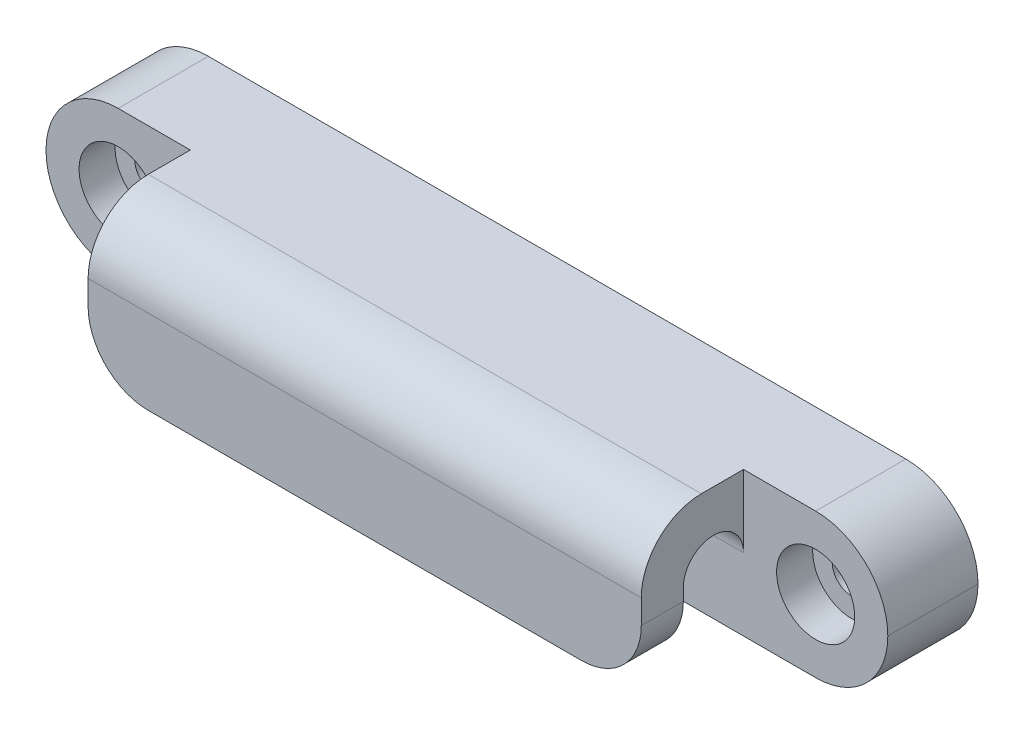
SolidWorks part; units mm, degrees
ref_plane "Front Plane" through (0, 0, 0) normal (0, 0, 1) x (1, 0, 0)
ref_plane "Top Plane" through (0, 0, 0) normal (0, 1, 0) x (1, 0, 0)
ref_plane "Right Plane" through (0, 0, 0) normal (1, 0, 0) x (0, 0, -1)
sketch "Sketch1" plane through (0, 0, 0) normal (0, 0, 1) x (1, 0, 0)
  line L1 (-35, 6) -> (35, 6)
  line L2 (-35, 6) -> (-35, -6)
  line L3 (-35, -6) -> (35, -6)
  line L4 (35, 6) -> (35, -6)
  line L5 (-35, 6) -> (35, -6) construction
  line L6 (-35, -6) -> (35, 6) construction
  point P0 (0, 0)
  dimension "D1" = 12
  dimension "D2" = 70
extrude "Boss-Extrude1" add sketch "Sketch1" along normal blind 16
sketch "Sketch2" plane through (-35, 0, 0) normal (-1, 0, 0) x (0, 0, 1)
  line L0 (0, 6) -> (16, -6) construction
  line L1 (0, 0) -> (16, 0) construction
  line L2 (16, 6) -> (16, -6) construction
  circle A0 centre (10, 0) radius 2.5
  dimension "D1" = 5
  dimension "D2" = 6
extrude "Cut-Extrude1" cut sketch "Sketch2" against normal through all
sketch "Sketch3" plane through (-35, 0, 0) normal (-1, 0, 0) x (0, 0, 1)
  line L0 (7.5, 0) -> (12.5, 0)
  line L1 (12.5, 0) -> (12.5, -7.6619)
  line L2 (12.5, -7.6619) -> (7.5, -7.6619)
  line L3 (7.5, -7.6619) -> (7.5, 0)
  circle A0 centre (10, 0) radius 2.5 construction
extrude "Cut-Extrude2" cut sketch "Sketch3" against normal through all
sketch "Sketch8" plane through (0, 0, 16) normal (0, 0, 1) x (1, 0, 0)
  line L0 (0, 0) -> (0, 6) construction
  line L1 (35, 6) -> (-35, 6) construction
  line L2 (-35, -6) -> (-35, 6)
  line L3 (-35, 6) -> (-23, 6)
  line L4 (-23, 6) -> (-23, -6)
  line L5 (-35, -6) -> (35, -6) construction
  line L6 (-23, -6) -> (-35, -6)
  line L7 (23, 6) -> (23, -6)
  line L8 (35, 6) -> (23, 6)
  line L9 (35, -6) -> (35, 6)
  line L10 (23, -6) -> (35, -6)
  dimension "D1" = 12
  dimension "D2" = 12
extrude "Cut-Extrude6" cut sketch "Sketch8" against normal blind 8.5
fillet "Fillet2" radius 5 1 edges at (0, 6, 16)
sketch "Sketch9" plane through (0, 0, 7.5) normal (0, 0, 1) x (1, 0, 0)
  line L0 (-35, 0) -> (0, 0) construction
  line L1 (-35, 6) -> (-35, -6) construction
  line L2 (0, 0) -> (0, 6) construction
  line L3 (-23, 6) -> (23, 6) construction
  circle A0 centre (-29, 0) radius 1.625
  circle A1 centre (29, 0) radius 1.625
  dimension "D1" = 3.25
  dimension "D2" = 6
extrude "Cut-Extrude7" cut sketch "Sketch9" against normal through all
sketch "Sketch10" plane through (0, 0, 7.5) normal (0, 0, 1) x (1, 0, 0)
  line L0 (0, 0) -> (0, 6) construction
  line L1 (-23, 6) -> (23, 6) construction
  circle A0 centre (-29, 0) radius 3.25
  circle A1 centre (29, 0) radius 3.25
  dimension "D1" = 6.5
extrude "Cut-Extrude8" cut sketch "Sketch10" against normal blind 3
fillet "Fillet3" radius 6 4 edges at (35, 6, 3.75) (35, -6, 3.75) (-35, 6, 3.75) (-35, -6, 3.75)
fillet "Fillet5" radius 5 2 edges at (-23, -6, 14.25) (23, -6, 14.25)
